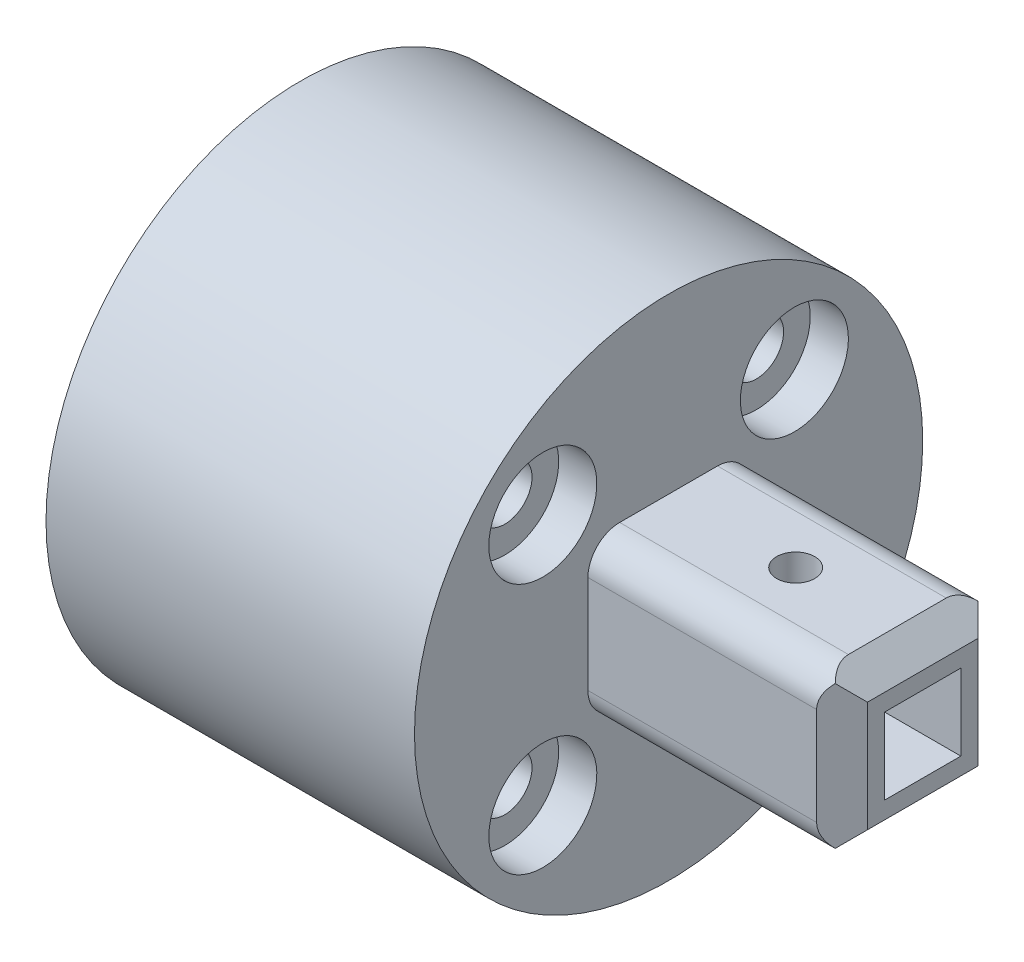
SolidWorks part; units mm, degrees
ref_plane "前视基准面" through (0, 0, 0) normal (0, 0, 1) x (1, 0, 0)
ref_plane "上视基准面" through (0, 0, 0) normal (0, 1, 0) x (1, 0, 0)
ref_plane "右视基准面" through (0, 0, 0) normal (1, 0, 0) x (0, 0, -1)
sketch "草图1" plane through (0, 0, 0) normal (1, 0, 0) x (0, 0, -1)
  circle A0 centre (0, 0) radius 20
  dimension "D1" = 40
extrude "凸台-拉伸1" add sketch "草图1" along normal blind 10
sketch "草图2" plane through (0, 0, 0) normal (-1, 0, 0) x (0, 0, 1)
  line L1 (-7.5, -15.25) -> (7.5, -15.25)
  line L2 (-7.5, -15.25) -> (-7.5, 15.25)
  line L3 (-7.5, 15.25) -> (7.5, 15.25)
  line L4 (7.5, -15.25) -> (7.5, 15.25)
  line L5 (-7.5, -15.25) -> (7.5, 15.25) construction
  line L6 (-7.5, 15.25) -> (7.5, -15.25) construction
  point P0 (0, 0)
  dimension "D1" = 15
  dimension "D2" = 30.5
extrude "切除-拉伸1" cut sketch "草图2" against normal blind 4
sketch "草图3" plane through (4, 0, 0) normal (-1, 0, 0) x (0, 0, 1)
  circle A0 centre (0, 0) radius 8.75
  dimension "D1" = 17.5
extrude "切除-拉伸2" cut sketch "草图3" along normal blind 4
sketch "草图4" plane through (0, 0, 0) normal (-1, 0, 0) x (0, 0, 1)
  line L1 (-9, -16) -> (9, -16)
  line L2 (-9, -16) -> (-9, 16)
  line L3 (-9, 16) -> (9, 16)
  line L4 (9, -16) -> (9, 16)
  line L5 (-9, -16) -> (9, 16) construction
  line L6 (-9, 16) -> (9, -16) construction
  circle A0 centre (0, 0) radius 20
  dimension "D3" = 40
  dimension "D1" = 32
  dimension "D2" = 18
extrude "凸台-拉伸2" add sketch "草图4" along normal blind 19
fillet "圆角1" radius 3 4 edges at (-9.5, -16, -9) (-9.5, -16, 9) (-9.5, 16, -9) (-9.5, 16, 9)
sketch "草图5" plane through (-19, 0, 0) normal (-1, 0, 0) x (0, 0, 1)
  line L0 (-6, -16) -> (6, -16) construction
  line L1 (6, 16) -> (-6, 16) construction
  circle A0 centre (0, -16) radius 2.5
  circle A1 centre (0, 16) radius 2.5
  dimension "D1" = 5
  dimension "D2" = 5
extrude "切除-拉伸3" cut sketch "草图5" against normal blind 20
fillet "圆角2" radius 3 4 edges at (-9.5, -16, -2.5) (-9.5, -16, 2.5) (-9.5, 16, -2.5) (-9.5, 16, 2.5)
sketch "草图6" plane through (10, 0, 0) normal (1, 0, 0) x (0, 0, -1)
  line L0 (0, 0) -> (20, 0) construction
  line L1 (0, 0) -> (18.216, -18.216) construction
  circle A0 centre (0, 0) radius 14 construction
  circle A2 centre (9.8995, -9.8995) radius 2.15
  circle A3 centre (0, 0) radius 14 construction
  circle A4 centre (-9.8995, -9.8995) radius 2.15
  circle A5 centre (0, 0) radius 14 construction
  circle A6 centre (-9.8995, 9.8995) radius 2.15
  circle A7 centre (0, 0) radius 14 construction
  circle A8 centre (9.8995, 9.8995) radius 2.15
  point P21 (0, 0)
  dimension "D1" = 28
  dimension "D3" = 4.3
  dimension "D2" = 45
  dimension "D4" = 4
extrude "切除-拉伸4" cut sketch "草图6" against normal blind 43
fillet "圆角3" radius 1 8 edges at (-9.5, -11.8523, 9) (-9.5, -7.9467, 9) (-9.5, -11.8523, -9) (-9.5, -7.9467, -9) (-9.5, 7.9467, -9) (-9.5, 11.8523, -9) (-9.5, 7.9467, 9) (-9.5, 11.8523, 9)
sketch "草图7" plane through (10, 0, 0) normal (1, 0, 0) x (0, 0, -1)
  circle A0 centre (9.8995, -9.8995) radius 4.25
  dimension "D1" = 8.5
extrude "切除-拉伸5" cut sketch "草图7" against normal blind 3
pattern_circular "阵列(圆周)1" count 4 over 360 about axis through (10, 0, 0) along (1, 0, 0) of "切除-拉伸5"
sketch "草图8" plane through (10, 0, 0) normal (1, 0, 0) x (0, 0, -1)
  line L1 (6.35, -6.35) -> (-6.35, -6.35)
  line L2 (6.35, -6.35) -> (6.35, 6.35)
  line L3 (6.35, 6.35) -> (-6.35, 6.35)
  line L4 (-6.35, -6.35) -> (-6.35, 6.35)
  line L5 (6.35, -6.35) -> (-6.35, 6.35) construction
  line L6 (6.35, 6.35) -> (-6.35, -6.35) construction
  point P0 (0, 0)
  dimension "D1" = 12.7
  dimension "D2" = 12.7
extrude "凸台-拉伸3" add sketch "草图8" along normal blind 20
sketch "草图9" plane through (30, 0, 0) normal (1, 0, 0) x (0, 0, -1)
  line L1 (3, -3) -> (-3, -3)
  line L2 (3, -3) -> (3, 3)
  line L3 (3, 3) -> (-3, 3)
  line L4 (-3, -3) -> (-3, 3)
  line L5 (3, -3) -> (-3, 3) construction
  line L6 (3, 3) -> (-3, -3) construction
  point P0 (0, 0)
  dimension "D1" = 6
  dimension "D2" = 6
extrude "切除-拉伸6" cut sketch "草图9" against normal blind 35
sketch "草图10" plane through (1, 0, 0) normal (-1, 0, 0) x (0, 0, 1)
  line L0 (-3, 3) -> (3, 3) construction
  line L1 (-1.5, 3) -> (1.5, 3)
  line L2 (-1.5, 3) -> (-1.5, 18)
  line L3 (-1.5, 18) -> (1.5, 18)
  line L4 (1.5, 3) -> (1.5, 18)
  arc A0 (2.3848, 15.25) -> (-2.3848, 15.25) centre (0, 16) ccw construction
  dimension "D1" = 3
  dimension "D2" = 1.5
extrude "切除-拉伸7" cut sketch "草图10" against normal blind 5
sketch "草图11" plane through (1, 0, 0) normal (-1, 0, 0) x (0, 0, 1)
  circle A0 centre (0, 16) radius 2.5
  dimension "D1" = 5
extrude "切除-拉伸8" cut sketch "草图11" against normal blind 5
sketch "草图12" plane through (0, -6.35, 0) normal (0, -1, 0) x (1, 0, 0)
  line L0 (10, 6.35) -> (10, -6.35) construction
  line L1 (30, 6.35) -> (10, 6.35) construction
  circle A0 centre (20, 0) radius 1.5
  dimension "D1" = 3
  dimension "D2" = 10
  dimension "D3" = 6.35
extrude "切除-拉伸9" cut sketch "草图12" against normal blind 17
chamfer "倒角1" distance 2 angle 45 4 edges at (30, 0, 6.35) (30, 6.35, 0) (30, 0, -6.35) (30, -6.35, 0)
fillet "圆角4" radius 3 1 edges at (6, 3, 0)
fillet "圆角5" radius 2.5 4 edges at (19, -6.35, -6.35) (19, -6.35, 6.35) (19, 6.35, 6.35) (19, 6.35, -6.35)
